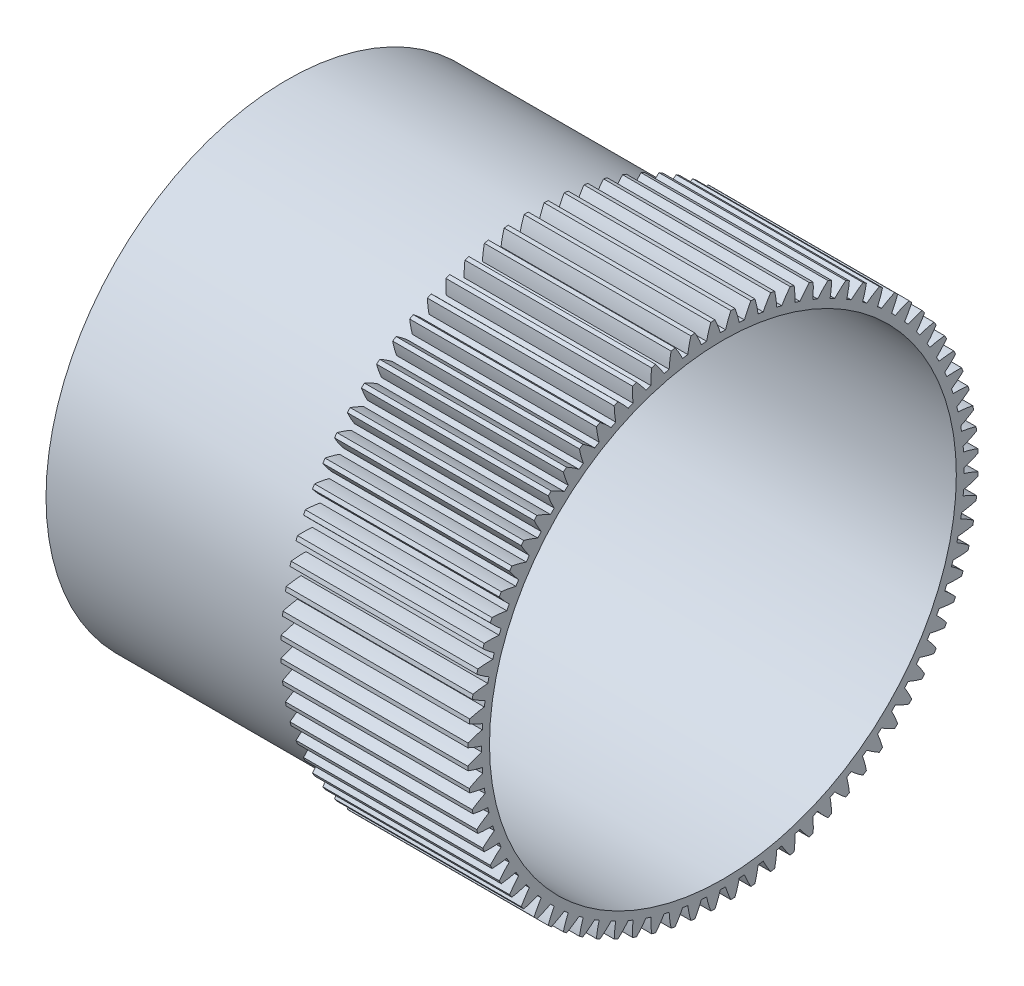
SolidWorks part; units mm, degrees
ref_plane "Plane1" through (0, 0, 0) normal (0, 0, 1) x (1, 0, 0)
ref_plane "Plane2" through (0, 0, 0) normal (0, 1, 0) x (1, 0, 0)
ref_plane "Plane3" through (0, 0, 0) normal (1, 0, 0) x (0, 0, -1)
other "Configuration Table"
sketch "HoldingSke" plane through (0, 0, 0) normal (0, 1, 0) x (1, 0, 0)
  line L0 (0, 0) -> (0.3473, -1.9696)
  line L1 (-15, 0) -> (100, 0) construction
  line L2 (0, 0) -> (-2.1039, 2.3779)
  line L3 (0, 0) -> (-11.863, 4.5341)
  line L4 (0, 0) -> (1.4996, 8.5048)
  line L5 (0, 0) -> (-46.8476, -17.4728)
  line L6 (0, 0) -> (-2.8599, -1.9296)
  line L7 (-2.1039, 2.3779) -> (8.6589, 51.2071)
  line L8 (-76.2, 54.61) -> (-76.1, 54.61)
  line L9 (-71.009, 38.7566) -> (-53.1078, 45.2721)
  line L10 (-76.2, 71.12) -> (104.1128, 71.12)
  line L11 (0, 0) -> (-3.45, 0)
  line L12 (-76.2, 101.6) -> (-76.181, 101.6)
  line L13 (24.9733, 27.94) -> (52.9518, 28.4284)
  line L14 (24.9733, 27.94) -> (24.9743, 27.94)
  line L15 (24.9733, 27.94) -> (100.4006, 29.5858)
  line L16 (-63.627, -0.5) -> (-12.827, -0.5)
  circle A0 centre (0, 0) radius 0.5
  circle A1 centre (0, 0) radius 19.374
  circle A2 centre (0, 0) radius 37.5
  circle A3 centre (0, 0) radius 0.5
  dimension "Num_teeth" = 80
  dimension "Pitch_radius" = 180.3128
  dimension "Width" = 3.45
sketch "BasProSke" plane through (0, 0, 0) normal (0, 1, 0) x (1, 0, 0)
  line L0 (-10, 0) -> (60, 0) construction
  line L1 (0, 0) -> (0, 20.5)
  line L2 (0, 0) -> (15, 0)
  line L3 (15, 0) -> (15, 20.5)
  line L4 (15, 20.5) -> (0, 20.5)
  dimension "Thickness" = 15
  dimension "Diameter" = 41
revolve "Base-Revolve" add sketch "BasProSke" angle 360 about L0
sketch "TooCutSke" plane through (0, 0, 0) normal (1, 0, 0) x (0, 0, -1)
  line L1 (0, 0) -> (0, 107) construction
  line L2 (0, 0) -> (-0.4259, 19.9955) construction
  line L3 (0, 0) -> (-1.5701, 39.9627) construction
  line L4 (-0.4259, 19.9955) -> (-0.7851, 19.9814) construction
  arc A0 (0.2101, 19.3729) -> (-0.2101, 19.3729) centre (0, 0) ccw
  arc A1 (0.6519, 20.515) -> (-0.6519, 20.515) centre (0, 0) ccw
  circle A2 centre (0, 0) radius 20 construction
  circle A3 centre (0, 0) radius 18.7939 construction
  arc A4 (-0.2101, 19.3729) -> (-0.6519, 20.515) centre (-7.8705, 17.0665) ccw
  arc A5 (0.6519, 20.515) -> (0.2101, 19.3729) centre (7.8705, 17.0665) ccw
extrude "ToothCut" cut sketch "TooCutSke" along normal through all
fillet "Breaks" [suppressed] radius 0.01 tangent propagation no
fillet "RootFillets" [suppressed] radius 0.126
pattern_circular "TeethCuts" count 80 every 4.5 about axis through (-10, 0, 0) along (1, 0, 0) of "ToothCut", "RootFillets", "Breaks"
sketch "HubNeaOneSke" plane through (0, 0, 0) normal (-1, 0, 0) x (0, 0, 1)
  circle A0 centre (0, 0) radius 19.374
  dimension "Diameter" = 38.748
extrude "HubNearOne" [suppressed] add sketch "HubNeaOneSke" along normal blind 35.0013
sketch "HubNeaBotSke" plane through (0, 0, 0) normal (-1, 0, 0) x (0, 0, 1)
  circle A0 centre (0, 0) radius 19.374
  dimension "Diameter" = 38.748
extrude "HubNearBoth" [suppressed] add sketch "HubNeaBotSke" along normal blind 17.5007
ref_plane "FarPln" through (15, 0, 0) normal (1, 0, 0) x (0, 0, -1)
sketch "HubFarSke" plane through (15, 0, 0) normal (1, 0, 0) x (0, 0, -1)
  circle A0 centre (0, 0) radius 19.374
  dimension "Diameter" = 38.748
extrude "HubFar" [suppressed] add sketch "HubFarSke" along normal blind 17.5007
sketch "BorSke" plane through (0, 0, 0) normal (1, 0, 0) x (0, 0, -1)
  circle A0 centre (0, 0) radius 0.5
  dimension "Diameter" = 1
extrude "Bore" cut sketch "BorSke" along normal mid plane 100.0026
sketch "KeySke" plane through (0, 0, 0) normal (1, 0, 0) x (0, 0, -1)
  line L0 (-0.05, 0) -> (-0.05, 0.6)
  line L1 (-0.05, 0.6) -> (0.05, 0.6)
  line L2 (0.05, 0.6) -> (0.05, 0)
  line L3 (0, 0) -> (0, 34) construction
  line L4 (-0.05, 0) -> (0.05, 0)
extrude "Keyway" [suppressed] cut sketch "KeySke" along normal mid plane 100.0026
pattern_circular "Keyway2" [suppressed] count 2 every 90 about axis through (-10, 0, 0) along (1, 0, 0)
sketch "Sketch1" plane through (15, 0, 0) normal (1, 0, 0) x (0, 0, -1)
  circle A0 centre (0, 0) radius 18.75
  dimension "D1" = 37.5
extrude "Cut-Extrude1" cut sketch "Sketch1" against normal through all
sketch "Sketch4" plane through (0, 0, 0) normal (-1, 0, 0) x (0, 0, 1)
  circle A0 centre (0, 0) radius 18.75
  circle A1 centre (0, 0) radius 19.374
  arc A2 (17.3567, 8.6079) -> (17.1659, 8.9823) centre (0, 0) ccw construction
  circle A3 centre (0, 0) radius 18.75 construction
extrude "Boss-Extrude5" add sketch "Sketch4" along normal blind 20
sketch "Sketch5" plane through (-20, 0, 0) normal (-1, 0, 0) x (0, 0, 1)
  circle A0 centre (0, 0) radius 18.75
  circle A1 centre (0, 0) radius 18.75 construction
extrude "Boss-Extrude6" add sketch "Sketch5" against normal blind 1
sketch "Sketch6" plane through (-20, 0, 0) normal (-1, 0, 0) x (0, 0, 1)
  circle A0 centre (0, 0) radius 2
  dimension "D1" = 4
extrude "Boss-Extrude7" add sketch "Sketch6" along normal blind 10
equation "' \"Module@HoldingSke\" = 6.35"
equation "' \"Num_teeth@HoldingSke\" = 12"
equation "' \"Ap@HoldingSke\" =  20"
equation "' \"Ap@HoldingSke\" = 20"
equation "' \"Width@HoldingSke\" = 0.5 * 25.4"
equation "' \"Hub_dia@HoldingSke\"= 1 * 25.4"
equation "' \"Hub_dia@HoldingSke\" = 1 * 25.4"
equation "' \"Overall_len@HoldingSke\" = 1.0 * 25.4"
equation "' \"Bore@HoldingSke\" = 0.75 * 25.4"
equation "' \"T_dim@HoldingSke\" = 0.1 * 25.4"
equation "' \"Width@KeySke\" = 0.25 * 25.4"
equation "' \"Show_teeth@HoldingSke\" = 13"
equation "' \"Backlash@HoldingSke\" = 0.009 * 25.4"
equation "' \"Addendum_fac@HoldingSke\" = 1.0"
equation "' \"Dedendum_fac@HoldingSke\" = 1.25"
equation "' \"Dedendum_add@HoldingSke\" = 0.00005 * 25.4"
equation "' \"Clearance_fac@HoldingSke\" = 0.25"
equation "\"Pitch@HoldingSke\" = 1 / \"Module@HoldingSke\""
equation "\"Overcut_dia@TooCutSke\" = (\"Num_teeth@HoldingSke\" + 2 * \"Addendum_fac@HoldingSke\") / \"Pitch@HoldingSke\" + 0.002 * 25.4"
equation "\"Pitch_dia@TooCutSke\" = \"Num_teeth@HoldingSke\" / \"Pitch@HoldingSke\""
equation "\"Base_dia@TooCutSke\" = \"Num_teeth@HoldingSke\" / \"Pitch@HoldingSke\" * cos((\"Ap@HoldingSke\"  * 3.14159265 / 180))"
equation "\"Root_dia@TooCutSke\" = (\"Num_teeth@HoldingSke\" + 2) / \"Pitch@HoldingSke\" - 2 * (\"Addendum_fac@HoldingSke\" + \"Dedendum_fac@HoldingSke\") / \"Pitch@HoldingSke\" - \"Dedendum_add@HoldingSke\" * 2"
equation "\"Half_ang@TooCutSke\" = 180 / \"Num_teeth@HoldingSke\""
equation "\"Half_CT@TooCutSke\" = \"Num_teeth@HoldingSke\" / \"Pitch@HoldingSke\" * sin((3.14159265 / 2 / \"Num_teeth@HoldingSke\")) / 2 - 7 * \"Backlash@HoldingSke\" / 4"
equation "\"Flank_rad@TooCutSke\" = \"Num_teeth@HoldingSke\" / \"Pitch@HoldingSke\" / 5"
equation "\"Radius@RootFillets\" = \"Clearance_fac@HoldingSke\" / \"Pitch@HoldingSke\" + \"Dedendum_add@HoldingSke\""
equation "\"Break_rad@Breaks\" = 0.02 / \"Pitch@HoldingSke\""
equation "\"Thickness@HoldingSke\" = \"Width@HoldingSke\""
equation "\"OAL@HoldingSke\" = \"Thickness@HoldingSke\""
equation "\"MHD@HoldingSke\" = (\"Num_teeth@HoldingSke\" + 2) / \"Pitch@HoldingSke\" - 2 * (\"Addendum_fac@HoldingSke\" + \"Dedendum_fac@HoldingSke\")  / \"Pitch@HoldingSke\" - \"Dedendum_add@HoldingSke\" * 2"
equation "\"MBD@HoldingSke\" = (\"Num_teeth@HoldingSke\" + 2) / \"Pitch@HoldingSke\" - 2 * (\"Addendum_fac@HoldingSke\" + \"Dedendum_fac@HoldingSke\")  / \"Pitch@HoldingSke\" - \"Dedendum_add@HoldingSke\" * 2 - 0.002 * 25.4"
equation "\"MHD@HoldingSke\" = ((sgn( \"MHD@HoldingSke\" - \"Hub_dia@HoldingSke\" )-1)*( \"MHD@HoldingSke\" - \"Hub_dia@HoldingSke\" ))/-2+ \"Hub_dia@HoldingSke\""
equation "\"MBD@HoldingSke\" = ((sgn( \"MBD@HoldingSke\" - \"Bore@HoldingSke\" )-1)*( \"MBD@HoldingSke\" - \"Bore@HoldingSke\" ))/-2+ \"Bore@HoldingSke\""
equation "\"OAL@HoldingSke\" = ((sgn( \"OAL@HoldingSke\" - \"Overall_len@HoldingSke\" )+1)*( \"OAL@HoldingSke\" - \"Overall_len@HoldingSke\" ))/2 + \"Overall_len@HoldingSke\" + 0.000002 * 25.4"
equation "\"Num_teeth@TeethCuts\" = int( \"Show_teeth@HoldingSke\" ) + 1"
equation "\"Num_teeth@TeethCuts\" = ((sgn( \"Num_teeth@TeethCuts\" - \"Num_teeth@HoldingSke\" )-1)*( \"Num_teeth@TeethCuts\" - \"Num_teeth@HoldingSke\" ))/-2+ \"Num_teeth@HoldingSke\""
equation "\"Num_teeth@TeethCuts\" = ((sgn( \"Num_teeth@TeethCuts\" - 2.0)+1)*( \"Num_teeth@TeethCuts\" - 2.0))/2 +2.0"
equation "\"Angle@TeethCuts\" = 360.0 / \"Num_teeth@HoldingSke\""
equation "\"Diameter@BasProSke\" = (\"Num_teeth@HoldingSke\" + 2 * \"Addendum_fac@HoldingSke\") / \"Pitch@HoldingSke\""
equation "' \"Fillet_rad@BasProSke\" =  \"Thickness@HoldingSke\" * 0.05"
equation "' \"Fillet_rad@BasProSke\" = \"Thickness@HoldingSke\" * 0.05"
equation "\"MHD@HoldingSke\" = ((sgn( \"MHD@HoldingSke\" - \"Root_dia@TooCutSke\" )-1)*( \"MHD@HoldingSke\" - \"Root_dia@TooCutSke\" ))/-2+ \"Root_dia@TooCutSke\""
equation "\"Diameter@HubNeaOneSke\" = \"MHD@HoldingSke\""
equation "\"Length@HubNearOne\" = \"OAL@HoldingSke\" - \"Thickness@BasProSke\""
equation "\"Diameter@HubNeaBotSke\" = \"MHD@HoldingSke\""
equation "\"Length@HubNearBoth\" = ( \"OAL@HoldingSke\" - \"Thickness@BasProSke\" ) / 2.0"
equation "\"Thickness@FarPln\" = \"Thickness@BasProSke\""
equation "\"Diameter@HubFarSke\" = \"MHD@HoldingSke\""
equation "\"Length@HubFar\" = ( \"OAL@HoldingSke\" - \"Thickness@BasProSke\" ) / 2.0"
equation "\"Diameter@BorSke\" = \"MBD@HoldingSke\""
equation "\"D1@Bore\" = \"OAL@HoldingSke\" * 2.0"
equation "\"D1@Keyway\" = \"OAL@HoldingSke\" * 2.0"
equation "\"Offset@KeySke\" = \"T_dim@HoldingSke\" + \"MBD@HoldingSke\" / 2.0"
